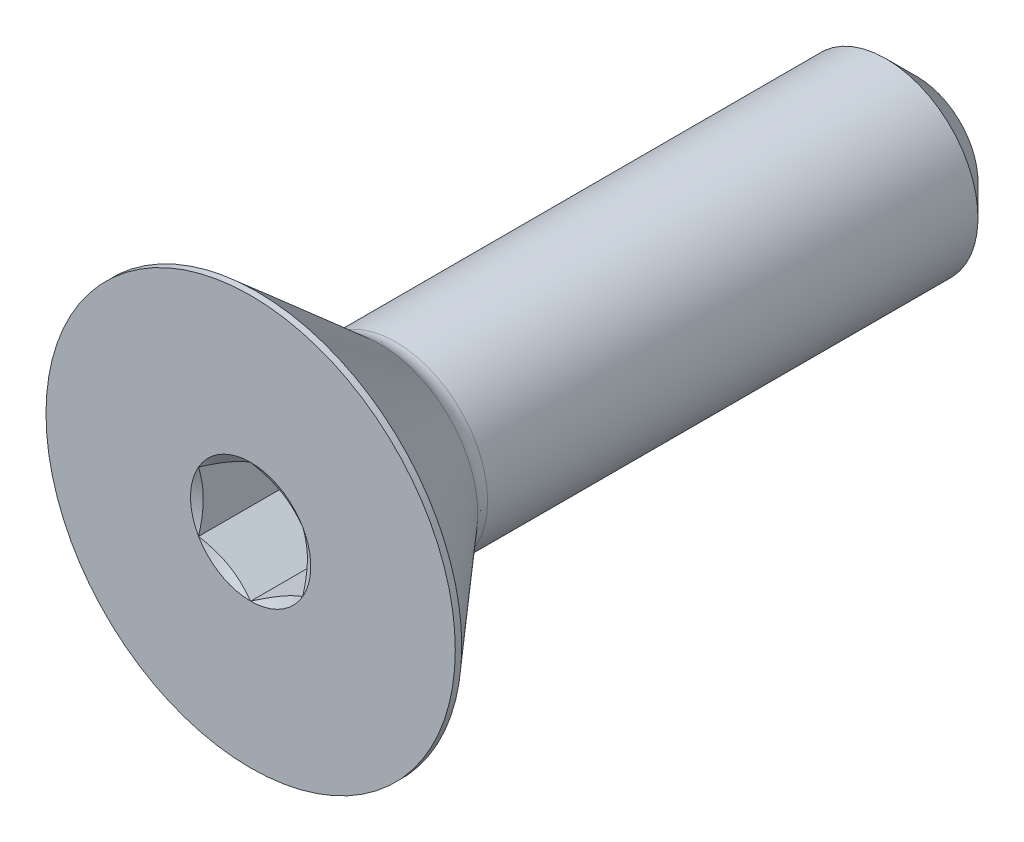
SolidWorks part; units mm, degrees
ref_plane "Front" through (0, 0, 0) normal (0, 0, 1) x (1, 0, 0)
ref_plane "Top" through (0, 0, 0) normal (0, 1, 0) x (1, 0, 0)
ref_plane "Right" through (0, 0, 0) normal (1, 0, 0) x (0, 0, -1)
sketch "Sketch1" plane through (0, 0, 0) normal (1, 0, 0) x (0, 0, -1)
  line L0 (0, 3.8989) -> (0.1232, 3.8989) construction
  line L1 (0.1232, 3.8989) -> (2.4638, 1.8642) construction
  line L2 (0, 1.7526) -> (12.7, 1.7526)
  line L3 (12.7, 1.7526) -> (12.7, 0)
  line L4 (12.7, 0) -> (0, 0)
  line L5 (0, 0) -> (0, 3.8989) construction
  line L6 (0, 3.8989) -> (0, -3.8989) construction
  line L7 (12.7, 1.7526) -> (12.7, -1.7526) construction
  line L8 (0, -3.8989) -> (0.1232, -3.8989) construction
  line L9 (0.1232, -3.8989) -> (2.4638, -1.8642) construction
  line L11 (0, 1.7526) -> (0, 0)
  line L12 (2.7624, 1.7526) -> (2.7624, 0) construction
  line L13 (-12.7, 0) -> (-12.7, 1.7526) construction
  arc A1 (2.4638, 1.8642) -> (2.7624, 1.7526) centre (2.7624, 2.2077) ccw construction
  dimension "D1" = 0.1232
  dimension "Min Thread" = 25.4
revolve "Revolve1" add sketch "Sketch1" angle 360 mid plane about L4
sketch "Sketch3" plane through (0, 0, -12.7) normal (0, 0, -1) x (-1, 0, 0)
  circle A0 centre (0, 0) radius 1.7526
curve "Helix/Spiral1" pitch 0.7937 height 12.7 turns 16
sketch "Sketch2" plane through (0, 0, 0) normal (1, 0, 0) x (0, 0, -1)
  line L0 (12.7, 1.7526) -> (13.3945, 1.7526)
  line L1 (13.3945, 1.7526) -> (13.0969, 1.237)
  line L2 (13.0969, 1.237) -> (12.9977, 1.237)
  line L3 (12.9977, 1.237) -> (12.7, 1.7526)
  line L4 (12.8488, 1.4948) -> (13.2457, 1.4948) construction
  dimension "D1" = 60
  dimension "D2" = 0.0992
  dimension "D3" = 0.3969
ref_plane "Plane2" through (0, 0, 12.7) normal (0, 0, 1) x (1, 0, 0)
chamfer "Chamfer1" distance 0.5953 angle 45 1 edges at (0, 1.7526, -12.7)
sweep "Cut-Sweep1" [suppressed] cut profiles "Sketch2" path "Helix/Spiral1"
sketch "Sketch7" plane through (0, 0, 0) normal (1, 0, 0) x (0, 0, -1)
  line L0 (0, 3.8989) -> (0.1232, 3.8989) construction
  line L1 (0.1232, 3.8989) -> (2.4638, 1.8642) construction
  line L2 (0, 3.8989) -> (0.1232, 3.8989)
  line L3 (0.1232, 3.8989) -> (2.4638, 1.8642)
  line L4 (2.7624, 1.7526) -> (2.7624, 0) construction
  line L5 (2.7624, 1.7526) -> (2.7624, 0)
  line L7 (0, 0) -> (0, 3.8989) construction
  line L8 (0, 0) -> (0, 3.8989)
  line L9 (0, 0) -> (2.7624, 0)
  line L10 (5.7417, 0) -> (-5.7417, 0) construction
  arc A0 (2.4638, 1.8642) -> (2.7624, 1.7526) centre (2.7624, 2.2077) ccw construction
  arc A1 (2.4638, 1.8642) -> (2.7624, 1.7526) centre (2.7624, 2.2077) ccw
revolve "Revolve2" add sketch "Sketch7" angle 360 mid plane about L9
ref_plane "Plane1" through (0, 0, -2.7624) normal (0, 0, 1) x (1, 0, 0)
sketch "Sketch8" plane through (0, 0, -2.7624) normal (0, 0, 1) x (1, 0, 0)
  circle A0 centre (0, 0) radius 1.7526
extrude "Boss-Extrude1" add sketch "Sketch8" against normal through all draft 46
sketch "Sketch5" plane through (0, 0, 0) normal (0, 0, 1) x (1, 0, 0)
  line L0 (0, 0) -> (-1.1457, 0) construction
  line L1 (0, 0) -> (-2.7496, 1.5875) construction
  line L2 (0, 0) -> (-2.7496, -1.5875) construction
  line L6 (0, 1.1457) -> (0, 0.9449) construction
  line L7 (0, 0.9449) -> (0, 0.7441) construction
  line L9 (0, 1.1457) -> (-0.9922, 0.5728)
  line L10 (-0.9922, 0.5728) -> (-0.9922, -0.5728)
  line L11 (-0.9922, -0.5728) -> (0, -1.1457)
  line L12 (0, -1.1457) -> (0.9922, -0.5728)
  line L13 (0.9922, -0.5728) -> (0.9922, 0.5728)
  line L14 (0.9922, 0.5728) -> (0, 1.1457)
  circle A0 centre (0, 0) radius 1.1457 construction
  circle A1 centre (0, 0) radius 0.9449 construction
  circle A2 centre (0, 0) radius 0.7441 construction
  circle A3 centre (0, 0) radius 0.9922 construction
  dimension "D3" = 1.4883
  dimension "D4" = 30
  dimension "D5" = 30
  dimension "Hex" = 1.9844
extrude "Cut-Extrude2" cut sketch "Sketch5" against normal blind 1.7247
sketch "Sketch6" plane through (0, 0, 0) normal (0, 0, 1) x (1, 0, 0)
  circle A0 centre (0, 0) radius 1.1457
extrude "Cut-Extrude3" cut sketch "Sketch6" against normal blind 1.7247 draft 60
sketch "Sketch9" [suppressed] plane through (0, 0, -3.6076) normal (0, 0, 1) x (1, 0, 0)
  circle A1 centre (0, 0) radius 2.413
  circle A2 centre (0, 0) radius 2.413
  point P0 (0, 2.413)
  dimension "D1" = 0
extrude "Boss-Extrude2" [suppressed] add sketch "Sketch9" against normal up to surface (15.4424 mm away)
sketch "Sketch10" plane through (0, 0, 0) normal (1, 0, 0) x (0, 0, -1)
  line L0 (12.7, 1.7526) -> (12.7, -1.7526) construction
  point P0 (11.5094, -1.7526)
  dimension "D1" = 1.1906
equation "\"D3@Helix/Spiral1\" = \"Lg@Sketch1\""
equation "\"D2@Sketch2\" = \"D4@Helix/Spiral1\" * .125"
equation "\"D3@Sketch2\" = \"D4@Helix/Spiral1\" * .5"
equation "\"D1@Chamfer1\" = \"D4@Helix/Spiral1\" * .75"
equation "\"D1@Cut-Extrude2\" = \"Head Ht@Sketch1\" * .7"
equation "\"D1@Sketch1\" = \"Head Ht@Sketch1\" * .05"
equation "\"D1@Sketch10\" = \"D4@Helix/Spiral1\" * 1.5"
equation "\"D1@Cut-Extrude3\" = \"D1@Cut-Extrude2\""
equation "\"D3@Sketch5\" = \"Hex@Sketch5\" * .75"
